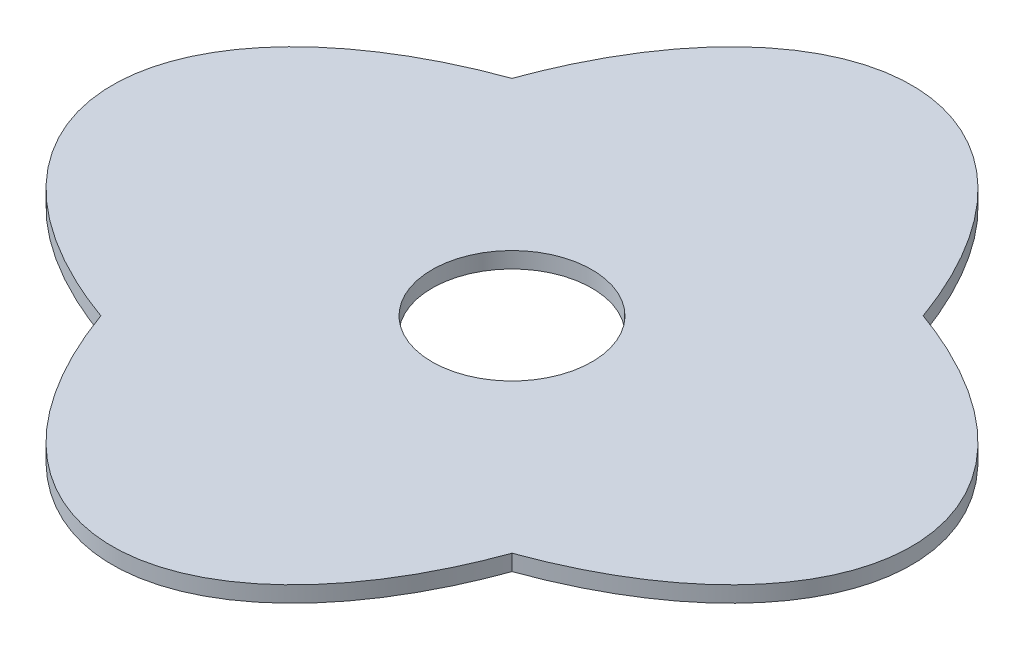
SolidWorks part; units mm, degrees
material "1060-H16"
ref_plane "Płaszczyzna przednia" through (0, 0, 0) normal (0, 0, 1) x (1, 0, 0)
ref_plane "Płaszczyzna górna" through (0, 0, 0) normal (0, 1, 0) x (1, 0, 0)
ref_plane "Płaszczyzna prawa" through (0, 0, 0) normal (1, 0, 0) x (0, 0, -1)
sketch "Szkic1" plane through (0, 0, 0) normal (0, 1, 0) x (1, 0, 0)
  line L0 (-61.0765, 17.9546) -> (45.7753, 41.4402)
  line L1 (-50, 0) -> (50, 0)
  line L2 (0, 50) -> (0, -50)
  line L3 (61.0765, 17.9546) -> (-45.7753, 41.4402)
  line L4 (-61.0765, -17.9546) -> (45.7753, -41.4402)
  line L5 (61.0765, -17.9546) -> (-45.7753, -41.4402)
  line L6 (34.2973, 52.5744) -> (-2.1147, -61.4701)
  line L7 (-34.2973, 52.5744) -> (2.1147, -61.4701)
  line L8 (34.2973, -52.5744) -> (-2.1147, 61.4701)
  line L9 (-34.2973, -52.5744) -> (2.1147, 61.4701)
  circle A0 centre (0, 0) radius 50
  circle A1 centre (0, 0) radius 30
  circle A2 centre (0, 0) radius 10
  ellipse E0 centre (0, 0) end of major axis (0, 50) minor radius 10
  ellipse E1 centre (0, 0) end of major axis (0, -50) minor radius 30
  ellipse E2 centre (0, 0) end of major axis (50, 0) minor radius 30
  point P5 (-25.7248, 25.7248)
  point P20 (-8.0582, 29.6078)
  point P34 (25.7248, -25.7248)
  point P39 (8.0582, -29.6078)
  point P41 (25.7248, 25.7248)
  dimension "D1" = 100
  dimension "D2" = 60
  dimension "D3" = 20
extrude "Dodanie-wyciągnięcie1" add sketch "Szkic1" along normal blind 2 contours E1 | E2
extrude "Wytnij-wyciągnięcie1" cut sketch "Szkic1<4>" along normal up to next contours L2 A2 L1 | L1 A2 L2 | L2 A2 L1 | L1 A2 L2 region at (-4.2441, 0, -4.2441) region at (-4.2441, 0, 4.2441) region at (4.2441, 0, -4.2441) region at (4.2441, 0, 4.2441)
sketch "Szkic1<4>" plane through (0, 0, 0) normal (0, 1, 0) x (1, 0, 0) same geometry as "Szkic1"
